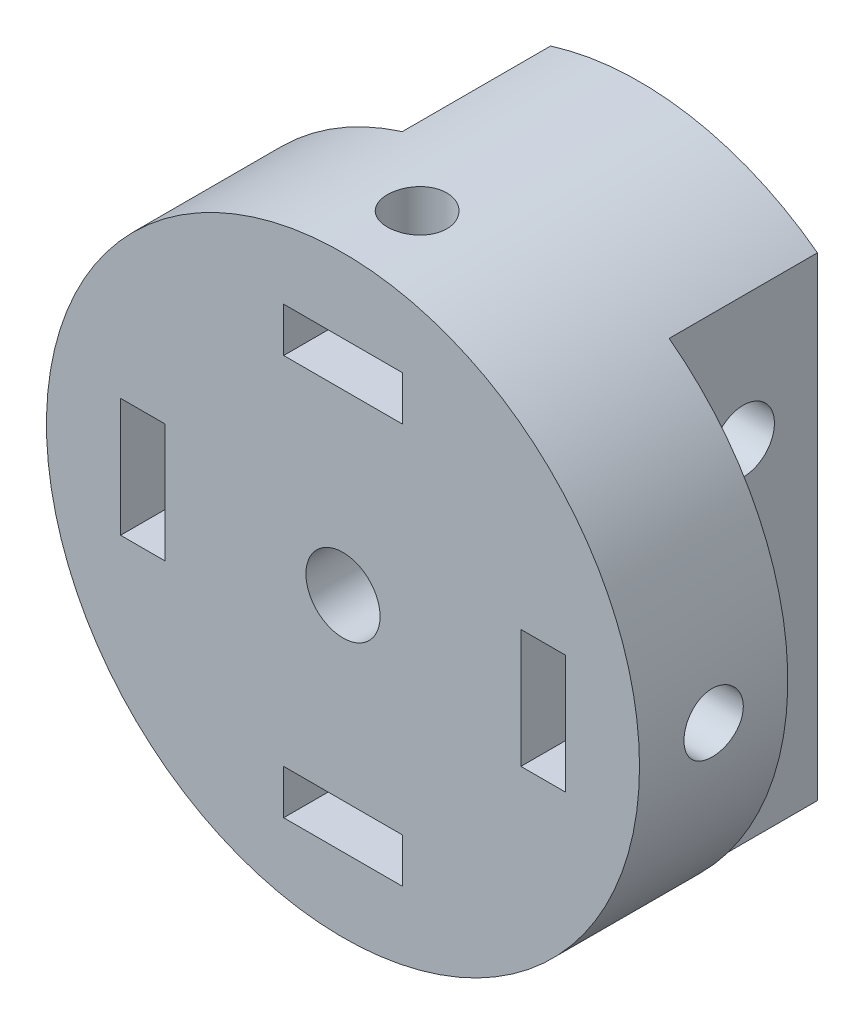
SolidWorks part; units mm, degrees
ref_plane "Front Plane" through (0, 0, 0) normal (1, 0, 0) x (0, 1, 0)
ref_plane "Top Plane" through (0, 0, 0) normal (0, 0, 1) x (0, 1, 0)
ref_plane "Right Plane" through (0, 0, 0) normal (0, 1, 0) x (-1, 0, 0)
sketch "Sketch3" plane through (0, 0, 0) normal (0, 0, 1) x (0, 1, 0)
  line L0 (0, 0) -> (25.4, 0) construction
  circle A0 centre (0, 0) radius 25.4
  circle A1 centre (0, 0) radius 3.175
  dimension "D1" = 50.8
  dimension "D2" = 6.35
extrude "base" add sketch "Sketch3" along normal blind 12.7
ref_plane "Plane1" through (-25.4, 0, 0) normal (-1, 0, 0) x (0, 0, 1)
sketch "Sketch6" plane through (0, 0, 0) normal (0, 0, -1) x (1, 0, 0)
  line L0 (0, 0) -> (15.24, 0) construction
  line L1 (15.24, 20.32) -> (-7.62, 20.32) construction
  line L2 (15.24, 20.32) -> (15.24, -20.32)
  line L3 (15.24, -20.32) -> (-7.62, -20.32) construction
  line L5 (-7.62, 24.2301) -> (-7.62, -24.2301)
  circle A0 centre (0, 0) radius 25.4 construction
  arc A1 (-7.62, 24.2301) -> (15.24, 20.32) centre (0, 0) cw
  arc A2 (-7.62, -24.2301) -> (15.24, -20.32) centre (0, 0) ccw
  circle A3 centre (0, 0) radius 3.175
  circle A4 centre (0, 0) radius 3.175 construction
  dimension "D1" = 22.86
  dimension "D2" = 15.24
extrude "upper_bolts_connection" add sketch "Sketch6" along normal blind 12.7
sketch "Sketch8" plane through (0, 0, -12.7) normal (0, 0, -1) x (1, 0, 0)
  line L1 (6.5991, 0) -> (3.2996, 5.715)
  line L2 (3.2996, 5.715) -> (-3.2996, 5.715)
  line L3 (-3.2996, 5.715) -> (-6.5991, 0)
  line L4 (-6.5991, 0) -> (-3.2996, -5.715)
  line L5 (-3.2996, -5.715) -> (3.2996, -5.715)
  line L6 (3.2996, -5.715) -> (6.5991, 0)
  circle A0 centre (0, 0) radius 5.715 construction
  dimension "D1" = 11.43
extrude "nut_hole" cut sketch "Sketch8" against normal blind 8.89
sketch "Sketch9" plane through (-7.62, 0, 0) normal (-1, 0, 0) x (0, 0, 1)
  circle A0 centre (-6.35, -9.525) radius 2.667
  circle A1 centre (-6.35, 9.525) radius 2.667
  circle A2 centre (-6.35, 9.525) radius 2.667 construction
  circle A3 centre (-6.35, -9.525) radius 2.667 construction
extrude "upper_boltholes" cut sketch "Sketch9" against normal up to next
sketch "Sketch13" plane through (-25.4, 0, 0) normal (-1, 0, 0) x (0, 0, 1)
  line L0 (0, 0) -> (12.7, 0) construction
  line L1 (12.2159, 0) -> (9.2829, 5.08) construction
  line L2 (9.2829, 5.08) -> (3.4171, 5.08) construction
  line L3 (3.4171, 5.08) -> (0.4841, 0)
  line L4 (0.4841, 0) -> (3.4171, -5.08)
  line L5 (3.4171, -5.08) -> (9.2829, -5.08) construction
  line L6 (9.2829, -5.08) -> (12.2159, 0) construction
  line L7 (12.7, -25.4) -> (12.7, 25.4) construction
  line L8 (3.4171, 5.08) -> (12.7, 5.08)
  line L9 (12.7, 5.08) -> (12.7, -5.08)
  line L10 (12.7, -5.08) -> (3.4171, -5.08)
  circle A0 centre (6.35, 0) radius 5.08 construction
  point P13 (12.7, 5.08)
  dimension "D1" = 10.16
extrude "nut_recess" cut sketch "Sketch13" against normal blind 3.81 from offset 6.35 offset against normal yes
sketch "Sketch14" plane through (-25.4, 0, 0) normal (-1, 0, 0) x (0, 0, 1)
  line L0 (0, 0) -> (12.7, 0) construction
  line L1 (12.7, -25.4) -> (12.7, 25.4) construction
  circle A0 centre (6.35, 0) radius 2.54
  dimension "D1" = 5.08
extrude "radial_bolt_hole" cut sketch "Sketch14" against normal blind 15.24
pattern_circular "CirPattern2" count 4 over 360 about axis through (0, 0, 12.7) along (0, 0, -1) of "radial_bolt_hole", "nut_recess" reverse direction yes
